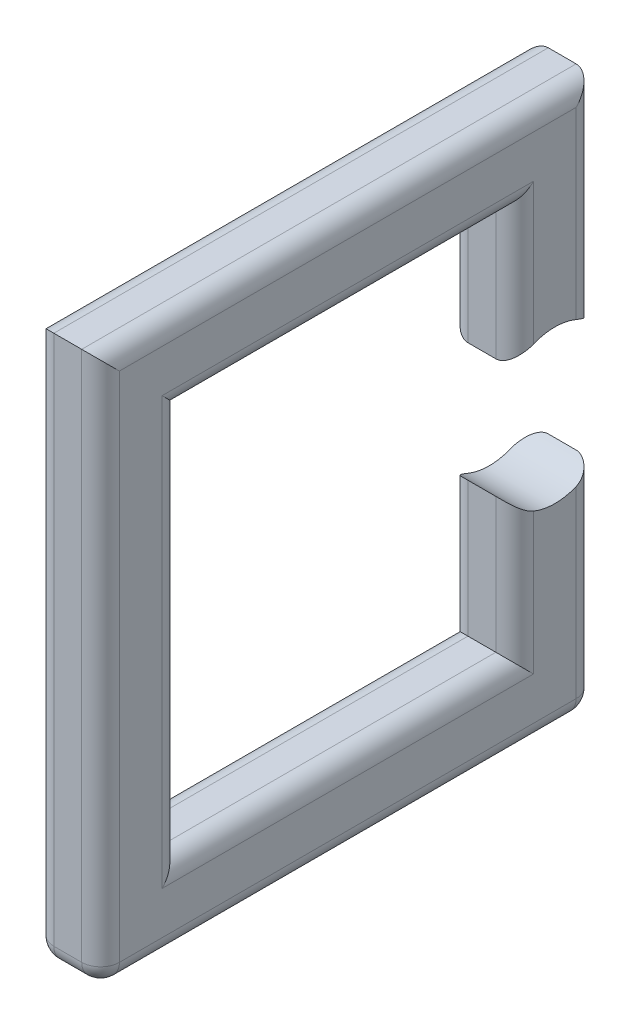
SolidWorks part; units mm, degrees
ref_plane "Front Plane" through (0, 0, 0) normal (0, 0, 1) x (1, 0, 0)
ref_plane "Top Plane" through (0, 0, 0) normal (0, 1, 0) x (1, 0, 0)
ref_plane "Right Plane" through (0, 0, 0) normal (1, 0, 0) x (0, 0, -1)
sketch "Sketch1" plane through (0, 0, 0) normal (1, 0, 0) x (0, 0, -1)
  line L0 (0, 0) -> (34.2483, 0) construction
  line L1 (-11.075, 12.91) -> (11.075, 12.91)
  line L2 (-11.075, 12.91) -> (-11.075, -12.91)
  line L3 (-11.075, -12.91) -> (11.075, -12.91)
  line L4 (11.075, 12.91) -> (11.075, 3.9516)
  line L5 (-16.405, 18.24) -> (16.405, 18.24)
  line L6 (-16.405, 18.24) -> (-16.405, -18.24)
  line L7 (-16.405, -18.24) -> (16.405, -18.24)
  line L8 (16.405, 18.24) -> (16.405, 3.9516)
  line L9 (11.075, -3.9516) -> (11.075, -12.91)
  line L10 (16.405, -3.9516) -> (16.405, -18.24)
  arc A0 (11.075, 3.9516) -> (16.405, 3.9516) centre (13.74, 1.3605) cw
  arc A1 (11.075, -3.9516) -> (16.405, -3.9516) centre (13.74, -1.3605) ccw
  point P14 (0, 0)
  point P15 (0, 0)
  point P16 (0, 0)
  point P17 (0, -12.91)
  point P18 (0, -18.24)
  dimension "D1" = 5.33
  dimension "D2" = 5.33
  dimension "D3" = 25.82
  dimension "D4" = 12.91
  dimension "D5" = 5.33
  dimension "D6" = 22.15
extrude "Boss-Extrude1" add sketch "Sketch1" along normal blind 4.35
fillet "Fillet1" radius 1.25 10 edges at (4.35, 0, 16.405) (4.35, 0, 11.075) (4.35, -12.91, 0) (4.35, -18.24, 0) (4.35, -11.0958, -16.405) (4.35, -8.4308, -11.075) (4.35, 12.91, 0) (4.35, 8.4308, -11.075) (4.35, 18.24, 0) (4.35, 11.0958, -16.405)
fillet "Fillet2" radius 1.25 14 edges at (3.9839, -17.8739, 16.0389) (3.9839, -17.8739, -16.0389) (1.55, -18.24, 16.405) (1.55, -18.24, -16.405) (0, 0, 16.405) (0, 0, 11.075) (0, 12.91, 0) (0, 18.24, 0) (0, 11.0958, -16.405) (0, 8.4308, -11.075) (0, -12.91, 0) (0, -18.24, 0) (0, -8.4308, -11.075) (0, -11.0958, -16.405)
equation "\"D4@Sketch1\"=\"D3@Sketch1\"/2"
equation "\"D1@Boss-Extrude1\"=4.5-0.15"
equation "\"D6@Sketch1\"=22+0.15"
